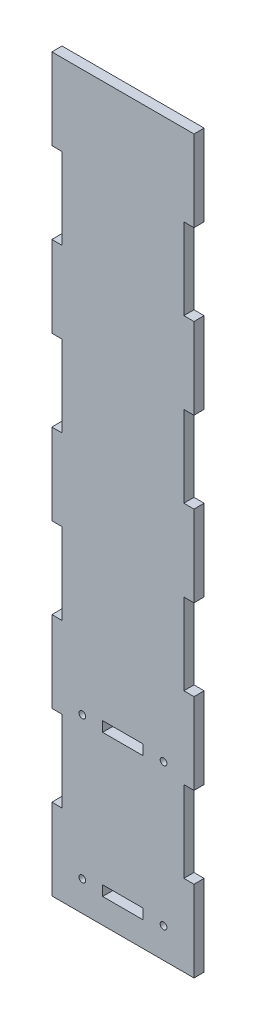
SolidWorks part; units mm, degrees
ref_plane "Front Plane" through (0, 0, 0) normal (0, 0, 1) x (1, 0, 0)
ref_plane "Top Plane" through (0, 0, 0) normal (0, 1, 0) x (1, 0, 0)
ref_plane "Right Plane" through (0, 0, 0) normal (1, 0, 0) x (0, 0, -1)
sketch "Sketch2" plane through (0, 0, 0) normal (0, 1, 0) x (0, 0, 1)
  line L1 (38.1, -44.45) -> (44.45, -44.45)
  line L2 (38.1, -44.45) -> (38.1, 44.45)
  line L3 (38.1, 44.45) -> (44.45, 44.45)
  line L4 (44.45, -44.45) -> (44.45, 44.45)
  dimension "D1" = 88.9
  dimension "D2" = 6.35
extrude "Boss-Extrude1" add sketch "Sketch2" along normal blind 457.2
ref_plane "Plane1" through (0, 0, 0) normal (1, 0, 0) x (0, 0, -1)
sketch "Sketch4" plane through (0, 0, 44.45) normal (0, 0, 1) x (1, 0, 0)
  line L0 (44.45, 457.2) -> (44.45, 406.4) construction
  line L1 (44.45, 457.2) -> (44.45, 0) construction
  line L2 (44.45, 406.4) -> (44.45, 355.6) construction
  line L3 (44.45, 355.6) -> (44.45, 304.8) construction
  line L4 (44.45, 304.8) -> (44.45, 254) construction
  line L5 (44.45, 254) -> (44.45, 203.2) construction
  line L6 (44.45, 203.2) -> (44.45, 152.4) construction
  line L7 (44.45, 152.4) -> (44.45, 101.6) construction
  line L8 (44.45, 101.6) -> (44.45, 50.8) construction
  line L9 (44.45, 50.8) -> (44.45, 0) construction
  line L11 (44.45, 406.4) -> (38.1, 406.4)
  line L12 (44.45, 406.4) -> (44.45, 355.6)
  line L13 (44.45, 355.6) -> (38.1, 355.6)
  line L14 (38.1, 406.4) -> (38.1, 355.6)
  line L15 (44.45, 304.8) -> (38.1, 304.8)
  line L16 (44.45, 304.8) -> (44.45, 254)
  line L17 (44.45, 254) -> (38.1, 254)
  line L18 (38.1, 304.8) -> (38.1, 254)
  line L19 (44.45, 203.2) -> (38.1, 203.2)
  line L20 (44.45, 203.2) -> (44.45, 152.4)
  line L21 (44.45, 152.4) -> (38.1, 152.4)
  line L22 (38.1, 203.2) -> (38.1, 152.4)
  line L23 (44.45, 101.6) -> (38.1, 101.6)
  line L24 (44.45, 101.6) -> (44.45, 50.8)
  line L25 (44.45, 50.8) -> (38.1, 50.8)
  line L26 (38.1, 101.6) -> (38.1, 50.8)
  dimension "D1" = 6.35
extrude "Cut-Extrude1" cut sketch "Sketch4" against normal through all
mirror "Mirror1" about plane through (0, 0, 0) normal (1, 0, 0) of "Cut-Extrude1"
sketch "Sketch5" plane through (0, 0, 38.1) normal (0, 0, -1) x (-1, 0, 0)
  line L0 (0, 0) -> (0, 124.5607) construction
  line L1 (-12.7, 110.8375) -> (12.7, 110.8375)
  line L2 (-12.7, 110.8375) -> (-12.7, 104.4875)
  line L3 (-12.7, 104.4875) -> (12.7, 104.4875)
  line L4 (12.7, 110.8375) -> (12.7, 104.4875)
  line L5 (-12.7, 21.9375) -> (12.7, 21.9375)
  line L6 (-12.7, 21.9375) -> (-12.7, 15.5875)
  line L7 (-12.7, 15.5875) -> (12.7, 15.5875)
  line L8 (12.7, 21.9375) -> (12.7, 15.5875)
  line L36 (38.1, 101.6) -> (44.45, 101.6)
  line L37 (44.45, 101.6) -> (44.45, 152.4)
  line L38 (44.45, 152.4) -> (38.1, 152.4)
  line L39 (38.1, 152.4) -> (38.1, 203.2)
  line L40 (38.1, 203.2) -> (44.45, 203.2)
  line L41 (44.45, 203.2) -> (44.45, 254)
  line L42 (44.45, 254) -> (38.1, 254)
  line L43 (38.1, 254) -> (38.1, 304.8)
  line L44 (38.1, 304.8) -> (44.45, 304.8)
  line L45 (44.45, 304.8) -> (44.45, 355.6)
  line L46 (44.45, 355.6) -> (38.1, 355.6)
  line L47 (38.1, 355.6) -> (38.1, 406.4)
  line L48 (38.1, 406.4) -> (44.45, 406.4)
  line L49 (44.45, 406.4) -> (44.45, 457.2)
  line L50 (44.45, 457.2) -> (-44.45, 457.2)
  line L51 (-44.45, 457.2) -> (-44.45, 406.4)
  line L52 (-44.45, 406.4) -> (-38.1, 406.4)
  line L53 (-38.1, 406.4) -> (-38.1, 355.6)
  line L54 (-38.1, 355.6) -> (-44.45, 355.6)
  line L55 (-44.45, 355.6) -> (-44.45, 304.8)
  line L56 (-44.45, 304.8) -> (-38.1, 304.8)
  line L57 (-38.1, 304.8) -> (-38.1, 254)
  line L58 (-38.1, 254) -> (-44.45, 254)
  line L59 (-44.45, 254) -> (-44.45, 203.2)
  line L60 (-44.45, 203.2) -> (-38.1, 203.2)
  line L61 (-38.1, 203.2) -> (-38.1, 152.4)
  line L62 (-38.1, 152.4) -> (-44.45, 152.4)
  line L63 (-44.45, 152.4) -> (-44.45, 101.6)
  line L64 (-44.45, 101.6) -> (-38.1, 101.6)
  line L65 (-38.1, 101.6) -> (-38.1, 50.8)
  line L66 (-38.1, 50.8) -> (-44.45, 50.8)
  line L67 (-44.45, 50.8) -> (-44.45, 0)
  line L68 (-44.45, 0) -> (44.45, 0)
  line L69 (44.45, 0) -> (44.45, 50.8)
  line L70 (44.45, 50.8) -> (38.1, 50.8)
  line L71 (38.1, 50.8) -> (38.1, 101.6)
  line L72 (38.1, 101.6) -> (44.45, 101.6)
  line L73 (44.45, 101.6) -> (44.45, 152.4)
  line L74 (44.45, 152.4) -> (38.1, 152.4)
  line L75 (38.1, 152.4) -> (38.1, 203.2)
  line L76 (38.1, 203.2) -> (44.45, 203.2)
  line L77 (44.45, 203.2) -> (44.45, 254)
  line L78 (44.45, 254) -> (38.1, 254)
  line L79 (38.1, 254) -> (38.1, 304.8)
  line L80 (38.1, 304.8) -> (44.45, 304.8)
  line L81 (44.45, 304.8) -> (44.45, 355.6)
  line L82 (44.45, 355.6) -> (38.1, 355.6)
  line L83 (38.1, 355.6) -> (38.1, 406.4)
  line L84 (38.1, 406.4) -> (44.45, 406.4)
  line L85 (44.45, 406.4) -> (44.45, 457.2)
  line L86 (44.45, 457.2) -> (-44.45, 457.2)
  line L87 (-44.45, 457.2) -> (-44.45, 406.4)
  line L88 (-44.45, 406.4) -> (-38.1, 406.4)
  line L89 (-38.1, 406.4) -> (-38.1, 355.6)
  line L90 (-38.1, 355.6) -> (-44.45, 355.6)
  line L91 (-44.45, 355.6) -> (-44.45, 304.8)
  line L92 (-44.45, 304.8) -> (-38.1, 304.8)
  line L93 (-38.1, 304.8) -> (-38.1, 254)
  line L94 (-38.1, 254) -> (-44.45, 254)
  line L95 (-44.45, 254) -> (-44.45, 203.2)
  line L96 (-44.45, 203.2) -> (-38.1, 203.2)
  line L97 (-38.1, 203.2) -> (-38.1, 152.4)
  line L98 (-38.1, 152.4) -> (-44.45, 152.4)
  line L99 (-44.45, 152.4) -> (-44.45, 101.6)
  line L100 (-44.45, 101.6) -> (-38.1, 101.6)
  line L101 (-38.1, 101.6) -> (-38.1, 50.8)
  line L102 (-38.1, 50.8) -> (-44.45, 50.8)
  line L103 (-44.45, 50.8) -> (-44.45, 0)
  line L104 (-44.45, 0) -> (44.45, 0)
  line L105 (44.45, 0) -> (44.45, 50.8)
  line L106 (44.45, 50.8) -> (38.1, 50.8)
  line L107 (38.1, 50.8) -> (38.1, 101.6)
  dimension "D2" = 6.35
  dimension "D3" = 6.35
  dimension "D4" = 25.4
  dimension "D5" = 25.4
  dimension "D6" = 82.55
  dimension "D7" = 15.5875
  dimension "D1" = 0
extrude "Cut-Extrude2" cut sketch "Sketch5" against normal through all contours L0 L7 L8 L5 | L7 L0 L5 L6 | L0 L3 L4 L1 | L3 L0 L1 L2 region at (6.35, 107.6625, 38.1) region at (-6.35, 107.6625, 38.1) region at (6.35, 18.7625, 38.1) region at (-6.35, 18.7625, 38.1)
sketch "Sketch6" plane through (0, 0, 44.45) normal (0, 0, 1) x (1, 0, 0)
  line L0 (25.4, 107.6625) -> (-25.4, 107.6625) construction
  line L1 (12.7, 110.8375) -> (-12.7, 110.8375) construction
  line L2 (12.7, 104.4875) -> (-12.7, 104.4875) construction
  line L3 (-25.4, 18.7625) -> (25.4, 18.7625) construction
  line L4 (12.7, 21.9375) -> (-12.7, 21.9375) construction
  line L5 (12.7, 15.5875) -> (-12.7, 15.5875) construction
  line L6 (0, 132.4794) -> (0, 71.8673) construction
  line L7 (-12.7, 110.8375) -> (-12.7, 104.4875) construction
  line L8 (12.7, 110.8375) -> (12.7, 104.4875) construction
  circle A0 centre (25.4, 107.6625) radius 2.0955
  circle A1 centre (-25.4, 107.6625) radius 2.0955
  circle A2 centre (-25.4, 18.7625) radius 2.0955
  circle A3 centre (25.4, 18.7625) radius 2.0955
  dimension "D1" = 4.191
  dimension "D2" = 12.7
extrude "Cut-Extrude3" cut sketch "Sketch6" against normal through all
